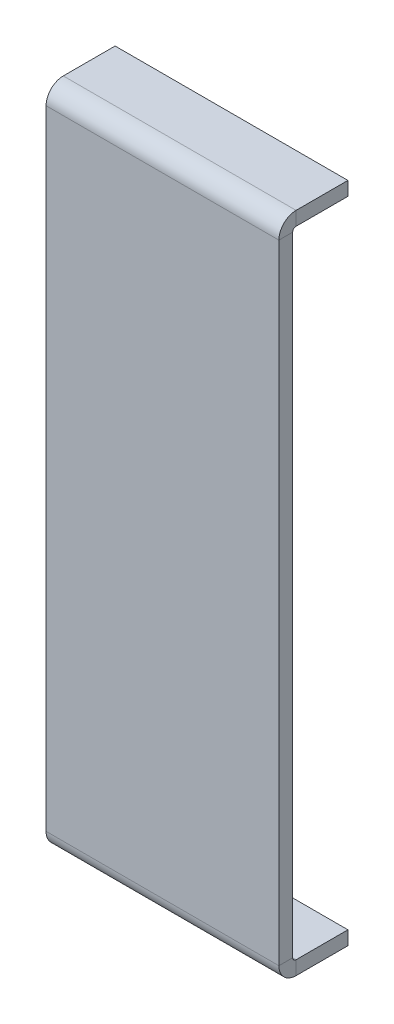
SolidWorks part; units mm, degrees
note: The reader was unsure of these and kept them because the rebuilt part matched: flange length of "Edge-Flange1", "Edge-Flange2".
material "AISI 316 Stainless Steel Sheet (SS)"
ref_plane "Front Plane" through (0, 0, 0) normal (0, 0, 1) x (1, 0, 0)
ref_plane "Top Plane" through (0, 0, 0) normal (0, 1, 0) x (1, 0, 0)
ref_plane "Right Plane" through (0, 0, 0) normal (1, 0, 0) x (0, 0, -1)
sketch "Sketch1" plane through (0, 0, 0) normal (0, 0, 1) x (1, 0, 0)
  line L1 (71.877, 97.8878) -> (21.2962, 97.8878)
  line L2 (71.877, 97.8878) -> (71.877, -46.1122)
  line L3 (71.877, -46.1122) -> (21.2962, -46.1122)
  line L4 (21.2962, 97.8878) -> (21.2962, -46.1122)
  line L5 (71.877, 97.8878) -> (21.2962, -46.1122) construction
  line L6 (71.877, -46.1122) -> (21.2962, 97.8878) construction
  point P0 (46.5866, 25.8878)
  dimension "D1" = 144
base flange "Base-Flange1" sketch "Sketch1" thickness 3 reverse thickness direction no parameters "D1"=0.7366
edge flange "Edge-Flange1" sketch "Sketch8" flange angle 90 flange length 15 flange position material inside bend radius 0.7366 thickness 3 relief rectangular parameters "D6"=10
sketch "Sketch8" plane through (0, -46.1122, -3) normal (0, -1, 0) x (-1, 0, 0)
  line L0 (-21.2962, 0) -> (-71.877, 0) construction
  line L1 (-21.2962, 0) -> (-71.877, 0)
  line L2 (-71.877, 0) -> (-71.877, 12)
  line L3 (-71.877, 12) -> (-21.2962, 12)
  line L4 (-21.2962, 12) -> (-21.2962, 0)
bend "EdgeBend1" bend radius 0.7366 bend angle 90 parameters "D5"=1
edge flange "Edge-Flange2" sketch "Sketch11" flange angle 90 flange length 15 flange position material inside bend radius 0.7366 thickness 3 relief rectangular parameters "D6"=10
sketch "Sketch11" plane through (0, 97.8878, -3) normal (0, 1, 0) x (1, 0, 0)
  line L0 (71.877, 0) -> (21.2962, 0) construction
  line L1 (71.877, 0) -> (21.2962, 0)
  line L2 (21.2962, 0) -> (21.2962, 12)
  line L3 (21.2962, 12) -> (71.877, 12)
  line L4 (71.877, 12) -> (71.877, 0)
bend "EdgeBend2" bend radius 0.7366 bend angle 90 parameters "D5"=2
sketch "Bend-Lines1" [suppressed] plane through (0, 0, 0) normal (0, 1, 0) x (1, 0, 0)
sketch "Bounding-Box1" [suppressed] plane through (0, 0, 0) normal (0, 1, 0) x (1, 0, 0)
sheet metal parameters "Sheet-Metal1" thickness 3 parameters "D1"=0.7366
flat pattern "Flat-Pattern1" [suppressed]
sketch "Bend-Lines2" plane through (0, 0, 0) normal (0, 1, 0) x (1, 0, 0)
sketch3d "Bounding-Box2" [suppressed]
  line L0 (59.2086, 96.8864, 0) -> (59.2086, -45.6404, 0) construction
  line L1 (9.1452, 96.8864, 0) -> (9.1452, -45.6404, 0) construction
  line L2 (59.2086, 96.8864, 0) -> (9.1452, 96.8864, 0) construction
  line L3 (59.2086, -45.6404, 0) -> (9.1452, -45.6404, 0) construction
sheet metal parameters "Sheet-Metal2" thickness 3 parameters "D1"=0.7366
flat pattern "Flat-Pattern1"
sketch "Bend-Lines2" plane through (0, 0, 0) normal (0, 0, 1) x (1, 0, 0)
  line L0 (21.0783, -43.6604) -> (71.1417, -43.6604) construction
  line L1 (21.0783, -43.6604) -> (71.1417, -43.6604) construction
sketch3d "Bounding-Box2" [suppressed]
  line L0 (71.1417, 96.8864, 0) -> (71.1417, -51.6804, 0) construction
  line L1 (21.0783, 96.8864, 0) -> (21.0783, -51.6804, 0) construction
  line L2 (71.1417, 96.8864, 0) -> (21.0783, 96.8864, 0) construction
  line L3 (71.1417, -51.6804, 0) -> (21.0783, -51.6804, 0) construction
bend of the flat pattern "Flatten-<EdgeBend1>1"
sheet metal parameters "Sheet-Metal3" thickness 3 parameters "D1"=0.7366
flat pattern "Flat-Pattern1"
sketch "Bend-Lines2" plane through (0, 0, 0) normal (0, 0, 1) x (1, 0, 0)
  line L0 (21.2962, -44.1322) -> (71.877, -44.1322) construction
  line L1 (21.2962, -44.1322) -> (71.877, -44.1322) construction
  line L2 (71.877, 95.9079) -> (21.2962, 95.9079) construction
  line L3 (71.877, 95.9079) -> (21.2962, 95.9079) construction
sketch3d "Bounding-Box2" [suppressed]
  line L0 (71.877, 108.9279, 0) -> (71.877, -57.1522, 0) construction
  line L1 (21.2962, 108.9279, 0) -> (21.2962, -57.1522, 0) construction
  line L2 (71.877, 108.9279, 0) -> (21.2962, 108.9279, 0) construction
  line L3 (71.877, -57.1522, 0) -> (21.2962, -57.1522, 0) construction
bend of the flat pattern "Flatten-<EdgeBend1>1"
bend of the flat pattern "Flatten-<EdgeBend2>1"
